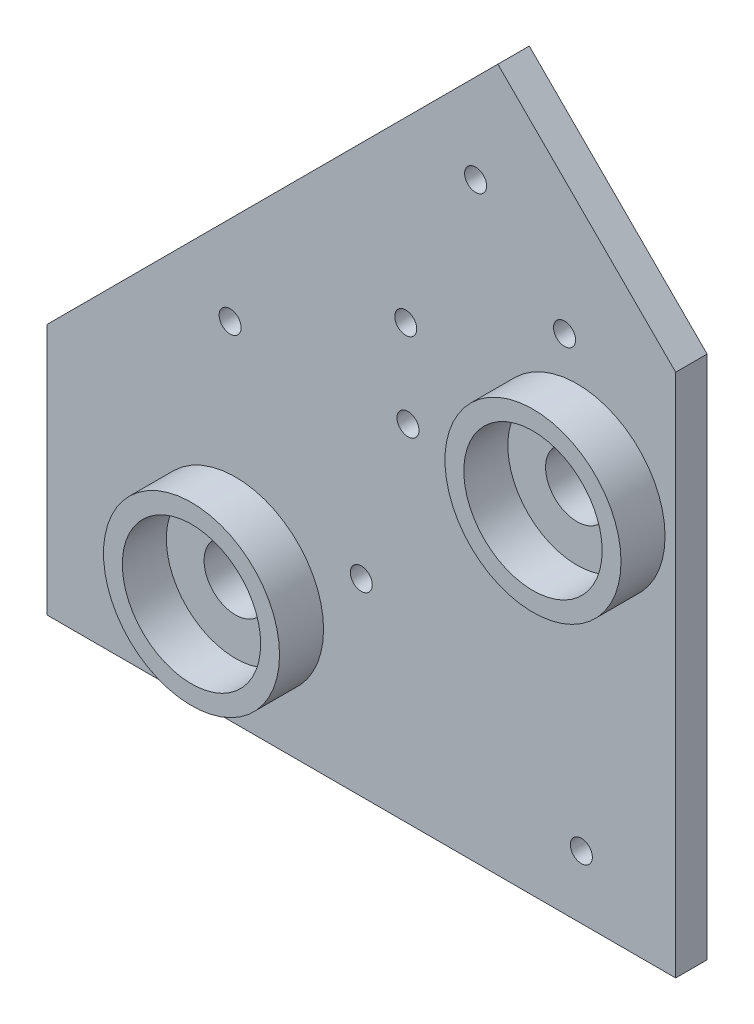
SolidWorks part; units mm, degrees
ref_plane "Front Plane" through (0, 0, 0) normal (0, 0, 1) x (1, 0, 0)
ref_plane "Top Plane" through (0, 0, 0) normal (0, 1, 0) x (1, 0, 0)
ref_plane "Right Plane" through (0, 0, 0) normal (1, 0, 0) x (0, 0, -1)
sketch "Sketch1" plane through (0, 0, 0) normal (0, 0, 1) x (1, 0, 0)
  line L0 (-50, 20) -> (21.7157, 91.7157)
  line L1 (6.5685, 20) -> (50, 20) construction
  line L2 (-50, 20) -> (-50, -20)
  line L3 (-50, -20) -> (50, -20)
  line L4 (50, 20) -> (50, -20)
  line L5 (-50, 20) -> (50, -20) construction
  line L6 (-50, -20) -> (50, 20) construction
  line L7 (-50, -20) -> (50, -20)
  line L11 (21.7157, 91.7157) -> (50, 63.4315)
  line L12 (50, 63.4315) -> (6.5685, 20) construction
  line L13 (-50, 0) -> (50, 0) construction
  line L14 (-50, 10) -> (50, 10) construction
  line L15 (-50, -10) -> (50, -10) construction
  line L16 (35.8579, 77.5736) -> (-21.7157, 20) construction
  line L17 (-50, 20) -> (6.5685, 20) construction
  line L18 (28.7868, 84.6447) -> (-35.8579, 20) construction
  line L19 (42.9289, 70.5025) -> (-7.5736, 20) construction
  line L20 (50, 63.4315) -> (50, 20)
  line L21 (18.1802, 74.0381) -> (32.3223, 59.8959) construction
  circle A0 centre (-20, 0) radius 5
  circle A1 centre (34.3058, 40) radius 5
  circle A2 centre (-35, -10) radius 1.75
  circle A3 centre (0, 10) radius 1.75
  circle A4 centre (35, -10) radius 1.75
  circle A5 centre (-20.8579, 35) radius 1.75
  circle A6 centre (18.1802, 74.0381) radius 1.75
  circle A7 centre (7.0711, 48.7868) radius 1.75
  circle A8 centre (7.4264, 35) radius 1.75
  circle A9 centre (32.3223, 59.8959) radius 1.75
  circle A10 centre (34.3058, 40) radius 4 construction
  point P0 (0, 0)
  dimension "D8" = 10
  dimension "D11" = 10
  dimension "D12" = 3.5
  dimension "D1" = 40
  dimension "D2" = 40
  dimension "D3" = 45
  dimension "D4" = 10
  dimension "D5" = 10
  dimension "D6" = 10
  dimension "D7" = 10
  dimension "D9" = 30
  dimension "D10" = 100
  dimension "D13" = 15
  dimension "D14" = 15
  dimension "D15" = 15
  dimension "D16" = 15
extrude "Boss-Extrude1" add sketch "Sketch1" along normal blind 5 contours L20 L11 L0 L2 L3 L4 A0 region at (6.1923, 23.5775, 0)
sketch "Sketch2" plane through (0, 0, 5) normal (0, 0, 1) x (1, 0, 0)
  circle A0 centre (-20, 0) radius 11
  circle A1 centre (-20, 0) radius 14
  circle A2 centre (34.3058, 40) radius 11
  circle A3 centre (34.3058, 40) radius 14
  dimension "D1" = 22
  dimension "D2" = 28
  dimension "D3" = 22
  dimension "D4" = 28
extrude "Boss-Extrude2" add sketch "Sketch2" along normal blind 7
